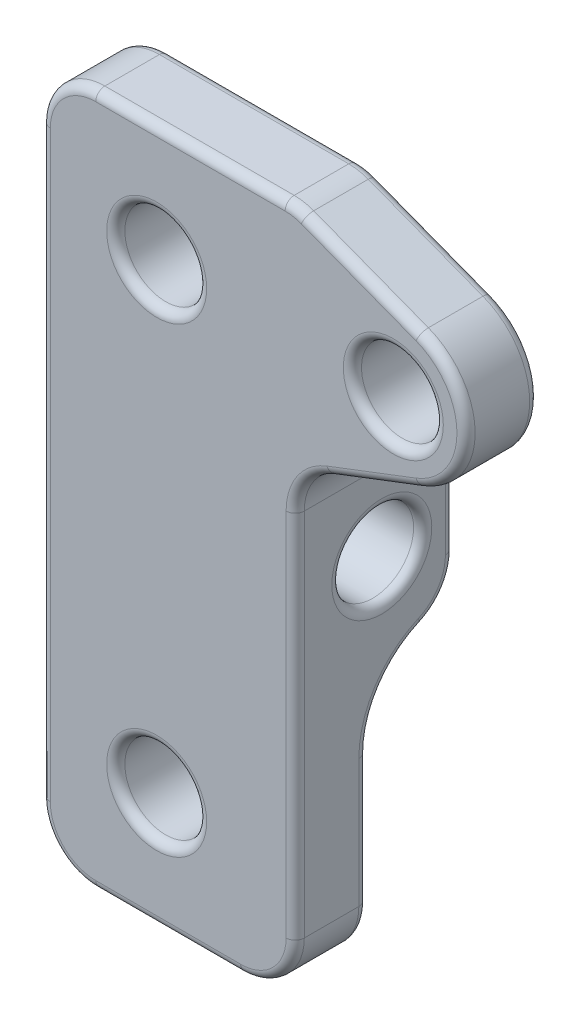
SolidWorks part; units mm, degrees
ref_plane "Front Plane" through (0, 0, 0) normal (0, 0, 1) x (1, 0, 0)
ref_plane "Top Plane" through (0, 0, 0) normal (0, 1, 0) x (1, 0, 0)
ref_plane "Right Plane" through (0, 0, 0) normal (1, 0, 0) x (0, 0, -1)
sketch "Sketch1" plane through (0, 0, 0) normal (0, 0, 1) x (1, 0, 0)
  line L0 (13.97, 38.1) -> (13.97, 0)
  line L1 (0, 0) -> (38.1, 0)
  line L2 (0, 0) -> (0, 38.1)
  line L3 (0, 38.1) -> (38.1, 38.1)
  line L4 (38.1, 0) -> (38.1, 38.1)
  line L5 (24.13, 38.1) -> (24.13, 0)
  line L6 (13.97, 38.1) -> (20.7979, 35.4855)
  line L7 (13.97, 25.4) -> (20.7979, 28.0145)
  circle A0 centre (19.3675, 31.75) radius 4.7625 construction
  circle A1 centre (19.3675, 31.75) radius 2.25
  circle A2 centre (6.35, 31.75) radius 2.25
  circle A3 centre (6.35, 6.35) radius 2.25
  circle A4 centre (19.3675, 31.75) radius 4
  point P17 (13.97, 25.4)
  dimension "D5" = 9.525
  dimension "D7" = 4.5
  dimension "D8" = 4.5
  dimension "D9" = 4.5
  dimension "D14" = 8
  dimension "D1" = 38.1
  dimension "D2" = 38.1
  dimension "D3" = 13.97
  dimension "D4" = 13.97
  dimension "D6" = 6.35
  dimension "D10" = 6.35
  dimension "D11" = 6.35
  dimension "D12" = 6.35
  dimension "D13" = 6.35
  dimension "D15" = 12.7
extrude "Boss-Extrude1" add sketch "Sketch1" against normal blind 4 contours L3 L2 L1 L0 A3 A2 | A4 L6 L0 L7 | A4 A1 region at (17.3324, 36.6581, 0) region at (7.0254, 19.05, 0) region at (22.5699, 33.9529, 0)
sketch "Sketch2" plane through (13.97, 0, 0) normal (1, 0, 0) x (0, 0, -1)
  line L0 (0, 25.4) -> (0, 0) construction
  line L2 (4, 0) -> (0, 0) construction
  line L3 (0, 23.05) -> (8.7625, 23.05)
  line L4 (0, 23.05) -> (0, 15.05)
  line L5 (0, 15.05) -> (8.7625, 15.05)
  line L6 (8.7625, 23.05) -> (8.7625, 15.05)
  circle A2 centre (4.7625, 19.05) radius 4.7625
  circle A3 centre (4.7625, 19.05) radius 2.25
  line M20 (4, 0) -> (4, 25.4)
  dimension "D1" = 4
  dimension "D3" = 19.05
  dimension "D5" = 9.525
  dimension "D7" = 4.5
  dimension "D2" = 4
  dimension "D4" = 4
extrude "Boss-Extrude2" add sketch "Sketch2" against normal up to surface (13.97 mm away) contours A3 L5 A2 L6 L3 M20 | A2 L6 L3 | A2 L5 L6 region at (13.97, 22.9569, -5.6737) region at (13.97, 22.6123, -8.3248) region at (13.97, 15.4877, -8.3248) up to face at (0, 19.05, -2)
extrude "Cut-Extrude1" cut sketch "Sketch2<3>" against normal up to next contours A3 M20 | A3 M20 region at (13.97, 19.05, -3.3841) region at (13.97, 19.05, -5.3213)
sketch "Sketch2<3>" plane through (13.97, 0, 0) normal (1, 0, 0) x (0, 0, -1) same geometry as "Sketch2"
fillet "Fillet3" radius 3 5 edges at (13.97, 25.4, -2) (13.97, 0, -2) (0, 0, -2) (13.97, 38.1, -2) (0, 38.1, -2)
fillet "Fillet5" radius 0.5 8 edges at (8.6, 6.35, 0) (8.6, 6.35, -4) (8.6, 31.75, 0) (8.6, 31.75, -4) (21.6175, 31.75, 0) (21.6175, 31.75, -4) (0, 19.05, -7.0125) (13.97, 21.3, -4.7625)
fillet "Fillet6" radius 5 2 edges at (6.985, 23.05, -4) (6.985, 15.05, -4)
fillet "Fillet7" radius 3 2 edges at (6.985, 23.05, -8.7625) (6.985, 15.05, -8.7625)
fillet "Fillet8" radius 0.5 36 edges at (23.3673, 31.7907, -4) (17.643, 36.6936, -4) (13.9608, 38.05, -4) (8.2076, 38.1, -4) (0.8787, 37.2213, -4) (0, 6.5278, -4) (0, 31.5722, -4) (0.8787, 0.8787, -4) (6.985, 0, -4) (13.0913, 0.8787, -4) (23.3675, 31.75, 0) (17.643, 36.6936, 0) (13.9608, 38.05, 0) (8.2076, 38.1, 0) (0.8787, 37.2213, 0) (0, 19.05, 0) (0, 19.05, -8.7625) (0.8787, 0.8787, 0) (6.985, 0, 0) (13.0913, 0.8787, 0) (13.97, 13.1682, 0) (13.97, 6.5278, -4) (13.97, 12.7835, -4.8097) (0, 12.7835, -4.8097) (13.97, 15.7345, -8.2767) (13.97, 19.05, -8.7625) (13.97, 22.237, -8.3558) (14.3457, 24.79, -5.204) (18.2999, 27.058, -4.0983) (0, 25.3165, -4.8097) (0, 22.3655, -8.2767) (0, 15.7345, -8.2767) (14.4983, 25.0366, 0) (18.3475, 27.0762, 0)
